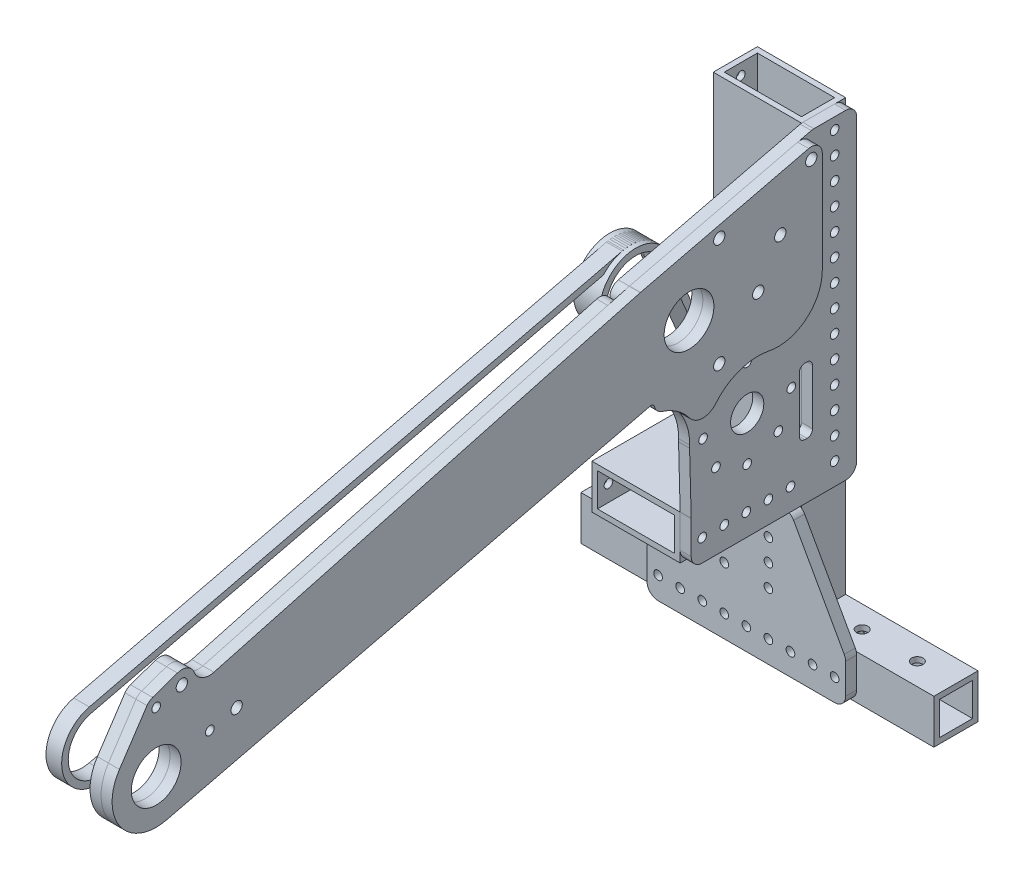
SolidWorks part; units mm, degrees
ref_plane "Alzado" through (0, 0, 0) normal (0, 0, 1) x (1, 0, 0)
ref_plane "Planta" through (0, 0, 0) normal (0, 1, 0) x (1, 0, 0)
ref_plane "Vista lateral" through (0, 0, 0) normal (1, 0, 0) x (0, 0, -1)
sketch "Croquis1" plane through (0, 0, 0) normal (0, 1, 0) x (1, 0, 0)
  line L1 (-101.6, -12.7) -> (101.6, -12.7)
  line L2 (-101.6, -12.7) -> (-101.6, 12.7)
  line L3 (-101.6, 12.7) -> (101.6, 12.7)
  line L4 (101.6, -12.7) -> (101.6, 12.7)
  line L5 (-101.6, -12.7) -> (101.6, 12.7) construction
  line L6 (-101.6, 12.7) -> (101.6, -12.7) construction
  point P0 (0, 0)
  dimension "D1" = 25.4
  dimension "D2" = 203.2
extrude "Saliente-Extruir1" add sketch "Croquis1" along normal blind 25.4
shell "Vaciado1" thickness 3.175 removed face at (-101.6, 12.7, 0) removed face at (101.6, 12.7, 0)
sketch "Croquis2" plane through (0, 25.4, 0) normal (0, 1, 0) x (1, 0, 0)
  line L0 (101.6, 12.7) -> (-101.6, 12.7) construction
  line L1 (-25.4, -12.7) -> (25.4, -12.7)
  line L2 (-25.4, -12.7) -> (-25.4, 12.7)
  line L3 (-25.4, 12.7) -> (25.4, 12.7)
  line L4 (25.4, -12.7) -> (25.4, 12.7)
  line L5 (-25.4, -12.7) -> (25.4, 12.7) construction
  line L6 (-25.4, 12.7) -> (25.4, -12.7) construction
  line L8 (-22.225, -9.525) -> (22.225, -9.525)
  line L9 (-22.225, -9.525) -> (-22.225, 9.525)
  line L10 (-22.225, 9.525) -> (22.225, 9.525)
  line L11 (22.225, -9.525) -> (22.225, 9.525)
  line L12 (-22.225, -9.525) -> (22.225, 9.525) construction
  line L13 (-22.225, 9.525) -> (22.225, -9.525) construction
  point P0 (0, 0)
  point P8 (0, 0)
  dimension "D1" = 50.8
  dimension "D2" = 3.175
  dimension "D3" = 3.175
extrude "Saliente-Extruir2" add sketch "Croquis2" along normal blind 247.65 separate body
sketch "Croquis3" plane through (0, 25.4, 0) normal (0, 1, 0) x (1, 0, 0)
  line L0 (0, 0) -> (0, 12.7) construction
  line L1 (25.4, 12.7) -> (-25.4, 12.7) construction
  circle A0 centre (-47.625, 0) radius 3.2639
  circle A1 centre (-79.375, 0) radius 3.2639
  circle A2 centre (79.375, 0) radius 3.2639
  circle A3 centre (47.625, 0) radius 3.2639
  dimension "D1" = 47.625
  dimension "D2" = 6.5278
  dimension "D3" = 31.75
extrude "Cortar-Extruir1" cut sketch "Croquis3" against normal through all
sketch "Croquis4" plane through (0, 0, 12.7) normal (0, 0, 1) x (1, 0, 0)
  line L0 (0, 25.4) -> (0, 139.6619) construction
  line L1 (-101.6, 25.4) -> (101.6, 25.4) construction
  line L2 (0, 139.6619) -> (-23.8125, 139.6619) construction
  circle A0 centre (0, 139.6619) radius 14.3129
  circle A1 centre (0, 139.6619) radius 23.8125 construction
  circle A2 centre (-23.8125, 139.6619) radius 2.4892 construction
  circle A3 centre (-11.9062, 160.2841) radius 2.4892
  circle A4 centre (11.9063, 160.2841) radius 2.4892
  circle A5 centre (23.8125, 139.6619) radius 2.4892 construction
  circle A6 centre (11.9062, 119.0397) radius 2.4892
  circle A7 centre (-11.9063, 119.0397) radius 2.4892
  dimension "D1" = 28.6258
  dimension "D3" = 47.625
  dimension "D4" = 4.9784
  dimension "D2" = 114.2619
  dimension "D6" = 23.8125
  dimension "D5" = 6
extrude "Cortar-Extruir2" cut sketch "Croquis4" against normal through all
sketch "Croquis8" plane through (0, 0, 12.7) normal (0, 0, 1) x (1, 0, 0)
  line L0 (0, 0) -> (0, 273.05) construction
  line L1 (-101.6, 12.7) -> (0, 12.7) construction
  line L2 (-101.6, 25.4) -> (-101.6, 0) construction
  line L3 (0, 12.7) -> (-12.7, 12.7) construction
  line L4 (0, 12.7) -> (12.7, 12.7) construction
  line L5 (-25.4, 273.05) -> (25.4, 273.05) construction
  line L6 (-12.7, 12.7) -> (-12.7, 25.4) construction
  circle A0 centre (0, 12.7) radius 2.4892
  circle A1 centre (-12.7, 12.7) radius 2.4892
  circle A2 centre (-25.4, 12.7) radius 2.4892
  circle A3 centre (-38.1, 12.7) radius 2.4892
  circle A4 centre (-50.8, 12.7) radius 2.4892
  circle A5 centre (0, 12.7) radius 2.4892
  circle A6 centre (-12.7, 12.7) radius 2.4892
  circle A7 centre (-25.4, 12.7) radius 2.4892
  circle A8 centre (-38.1, 12.7) radius 2.4892
  circle A9 centre (12.7, 12.7) radius 2.4892
  circle A10 centre (0, 12.7) radius 2.4892
  circle A11 centre (-12.7, 12.7) radius 2.4892
  circle A12 centre (-25.4, 12.7) radius 2.4892
  circle A13 centre (25.4, 12.7) radius 2.4892
  circle A14 centre (12.7, 12.7) radius 2.4892
  circle A15 centre (0, 12.7) radius 2.4892
  circle A16 centre (-12.7, 12.7) radius 2.4892
  circle A17 centre (38.1, 12.7) radius 2.4892
  circle A18 centre (25.4, 12.7) radius 2.4892
  circle A19 centre (12.7, 12.7) radius 2.4892
  circle A20 centre (0, 12.7) radius 2.4892
  circle A21 centre (12.7, 12.7) radius 2.4892
  circle A22 centre (25.4, 12.7) radius 2.4892
  circle A23 centre (38.1, 12.7) radius 2.4892
  circle A24 centre (50.8, 12.7) radius 2.4892
  circle A25 centre (-12.7, 25.4) radius 2.4892 [skipped]
  circle A26 centre (12.7, 25.4) radius 2.4892 [skipped]
  circle A27 centre (-12.7, 38.1) radius 2.4892
  circle A28 centre (12.7, 38.1) radius 2.4892
  circle A29 centre (-12.7, 50.8) radius 2.4892
  circle A30 centre (12.7, 50.8) radius 2.4892
  circle A31 centre (-12.7, 63.5) radius 2.4892
  circle A32 centre (12.7, 63.5) radius 2.4892
  circle A33 centre (-12.7, 76.2) radius 2.4892
  circle A34 centre (12.7, 76.2) radius 2.4892
  dimension "D1" = 4.9784
  dimension "D4" = 12.7
  dimension "D5" = 12.7
  dimension "D7" = 12.7
  dimension "D2" = 5
  dimension "D3" = 5
  dimension "D6" = 6
extrude "Cortar-Extruir4" cut sketch "Croquis8" against normal through all contours A4 | A3 | A2 | A1 | A0 | A9 | A13 | A17 | A24 | A28 | A29 | A30 | A31 | A32 | A34 | A33 | A27 region at (0, 12.7, 12.7) region at (-12.7, 12.7, 12.7) region at (-25.4, 12.7, 12.7) region at (-38.1, 12.7, 12.7) region at (-50.8, 12.7, 12.7) region at (12.7, 12.7, 12.7) region at (25.4, 12.7, 12.7) region at (38.1, 12.7, 12.7) region at (50.8, 12.7, 12.7) region at (12.7, 38.1, 12.7) region at (-12.7, 50.8, 12.7) region at (12.7, 50.8, 12.7) region at (-12.7, 63.5, 12.7) region at (12.7, 63.5, 12.7) region at (-12.7, 76.2, 12.7) region at (12.7, 76.2, 12.7)
sketch "Croquis6" plane through (0, 0, 12.7) normal (0, 0, 1) x (1, 0, 0)
  line L0 (25.4, 273.05) -> (25.4, 25.4) construction
  line L1 (-25.4, 88.646) -> (25.4, 88.646)
  line L2 (-25.4, 88.646) -> (-25.4, 114.046)
  line L3 (-25.4, 114.046) -> (25.4, 114.046)
  line L4 (25.4, 88.646) -> (25.4, 114.046)
  line L5 (-25.4, 88.646) -> (25.4, 114.046) construction
  line L6 (-25.4, 114.046) -> (25.4, 88.646) construction
  line L7 (-101.6, 25.4) -> (101.6, 25.4) construction
  line L9 (-22.225, 91.821) -> (22.225, 91.821)
  line L10 (-22.225, 91.821) -> (-22.225, 110.871)
  line L11 (-22.225, 110.871) -> (22.225, 110.871)
  line L12 (22.225, 91.821) -> (22.225, 110.871)
  line L13 (-22.225, 91.821) -> (22.225, 110.871) construction
  line L14 (-22.225, 110.871) -> (22.225, 91.821) construction
  point P0 (0, 101.346)
  point P11 (0, 101.346)
  dimension "D1" = 25.4
  dimension "D2" = 63.246
  dimension "D3" = 3.175
  dimension "D4" = 3.175
extrude "Saliente-Extruir3" add sketch "Croquis6" along normal blind 69.85 separate body
sketch "Croquis7" plane through (0, 114.046, 0) normal (0, 1, 0) x (1, 0, 0)
  line L0 (0, -12.7) -> (0, -82.55) construction
  line L1 (-25.4, -12.7) -> (25.4, -12.7) construction
  line L2 (25.4, -82.55) -> (-25.4, -82.55) construction
  line L3 (16.51, -12.7) -> (-16.51, -12.7)
  line L4 (25.4, -12.7) -> (-25.4, -12.7) construction
  line L5 (-16.51, -12.7) -> (-16.51, -34.798)
  line L6 (-13.208, -38.1) -> (13.208, -38.1)
  line L7 (16.51, -12.7) -> (16.51, -34.798)
  arc A0 (16.51, -34.798) -> (13.208, -38.1) centre (13.208, -34.798) cw
  arc A1 (-16.51, -34.798) -> (-13.208, -38.1) centre (-13.208, -34.798) ccw
  point P12 (0, -38.1)
  point P16 (16.51, -38.1)
  point P19 (-16.51, -38.1)
  dimension "D3" = 3.302
  dimension "D1" = 25.4
  dimension "D2" = 33.02
extrude "Cortar-Extruir3" cut sketch "Croquis7" against normal up to next (3.175 mm away)
sketch "Croquis11" plane through (25.4, 0, 0) normal (1, 0, 0) x (0, 0, -1)
  line L0 (0, -101.854) -> (-381, -101.854) construction
  line L1 (-82.55, 88.646) -> (-82.55, 114.046) construction
  line L2 (-82.55, 88.646) -> (-12.7, 88.646) construction
  line L6 (-517.96, -101.854) -> (-276.66, -101.854) construction
  line L7 (-517.96, -101.854) -> (-517.96, 139.446) construction
  line L8 (-517.96, 139.446) -> (-276.66, 139.446) construction
  line L9 (-276.66, -101.854) -> (-276.66, 139.446) construction
  circle A0 centre (-396.875, 145.796) radius 38.1
  dimension "D3" = 76.2
  dimension "D4" = 209.55
  dimension "D5" = 276.225
  dimension "D1" = 190.5
  dimension "D2" = 381
  dimension "D6" = 241.3
sketch "Croquis9" plane through (0, 0, 12.7) normal (0, 0, 1) x (1, 0, 0)
  line L0 (0, 0) -> (0, 273.05) construction
  line L1 (-25.4, 273.05) -> (25.4, 273.05) construction
  line L2 (50.8, 0) -> (-50.8, 0)
  line L3 (-101.6, 0) -> (101.6, 0) construction
  line L4 (-57.15, 6.35) -> (-57.15, 23.7481)
  line L5 (-101.6, 25.4) -> (101.6, 25.4) construction
  line L6 (-56.3451, 26.8425) -> (-27.2168, 79.0403)
  line L7 (-25.4, 273.05) -> (-25.4, 25.4) construction
  line L8 (-21.6717, 82.296) -> (21.6717, 82.296)
  line L9 (56.3451, 26.8425) -> (27.2168, 79.0403)
  line L10 (57.15, 6.35) -> (57.15, 23.7481)
  line L11 (-25.4, 88.646) -> (25.4, 88.646) construction
  circle A0 centre (-50.8, 12.7) radius 2.4892 construction
  arc A2 (-50.8, 0) -> (-57.15, 6.35) centre (-50.8, 6.35) cw
  arc A3 (-57.15, 23.7481) -> (-56.3451, 26.8425) centre (-50.8, 23.7481) cw
  arc A4 (-27.2168, 79.0403) -> (-21.6717, 82.296) centre (-21.6717, 75.946) cw
  arc A5 (27.2168, 79.0403) -> (21.6717, 82.296) centre (21.6717, 75.946) ccw
  arc A6 (57.15, 23.7481) -> (56.3451, 26.8425) centre (50.8, 23.7481) ccw
  arc A7 (50.8, 0) -> (57.15, 6.35) centre (50.8, 6.35) ccw
  circle A9 centre (-25.4, 12.7) radius 2.4892
  circle A10 centre (-25.4, 12.7) radius 2.4892
  circle A11 centre (-12.7, 12.7) radius 2.4892
  circle A12 centre (-12.7, 12.7) radius 2.4892
  circle A13 centre (0, 12.7) radius 2.4892
  circle A14 centre (0, 12.7) radius 2.4892
  circle A15 centre (0, 12.7) radius 2.4892
  circle A16 centre (0, 12.7) radius 2.4892
  circle A17 centre (12.7, 12.7) radius 2.4892
  circle A18 centre (12.7, 12.7) radius 2.4892
  circle A19 centre (-38.1, 12.7) radius 2.4892
  circle A20 centre (-38.1, 12.7) radius 2.4892
  circle A21 centre (-25.4, 12.7) radius 2.4892
  circle A22 centre (-25.4, 12.7) radius 2.4892
  circle A23 centre (-12.7, 12.7) radius 2.4892
  circle A24 centre (-12.7, 12.7) radius 2.4892
  circle A25 centre (0, 12.7) radius 2.4892
  circle A26 centre (0, 12.7) radius 2.4892
  circle A27 centre (-50.8, 12.7) radius 2.4892
  circle A28 centre (-50.8, 12.7) radius 2.4892
  circle A29 centre (-38.1, 12.7) radius 2.4892
  circle A30 centre (-38.1, 12.7) radius 2.4892
  circle A31 centre (25.4, 12.7) radius 2.4892
  circle A32 centre (25.4, 12.7) radius 2.4892
  circle A33 centre (38.1, 12.7) radius 2.4892
  circle A34 centre (38.1, 12.7) radius 2.4892
  circle A35 centre (-12.7, 12.7) radius 2.4892
  circle A36 centre (-12.7, 12.7) radius 2.4892
  circle A37 centre (0, 12.7) radius 2.4892
  circle A38 centre (0, 12.7) radius 2.4892
  circle A39 centre (12.7, 12.7) radius 2.4892
  circle A40 centre (12.7, 12.7) radius 2.4892
  circle A41 centre (25.4, 12.7) radius 2.4892
  circle A42 centre (25.4, 12.7) radius 2.4892
  circle A43 centre (-25.4, 12.7) radius 2.4892
  circle A44 centre (-25.4, 12.7) radius 2.4892
  circle A45 centre (-12.7, 12.7) radius 2.4892
  circle A46 centre (-12.7, 12.7) radius 2.4892
  circle A47 centre (50.8, 12.7) radius 2.4892
  circle A48 centre (50.8, 12.7) radius 2.4892
  circle A49 centre (38.1, 12.7) radius 2.4892
  circle A50 centre (38.1, 12.7) radius 2.4892
  circle A51 centre (25.4, 12.7) radius 2.4892
  circle A52 centre (25.4, 12.7) radius 2.4892
  circle A53 centre (12.7, 12.7) radius 2.4892
  circle A54 centre (12.7, 12.7) radius 2.4892
  circle A55 centre (0, 12.7) radius 2.4892
  circle A56 centre (0, 12.7) radius 2.4892
  circle A57 centre (12.7, 12.7) radius 2.4892
  circle A58 centre (12.7, 12.7) radius 2.4892
  circle A59 centre (-12.7, 76.2) radius 2.4892
  circle A60 centre (-12.7, 76.2) radius 2.4892
  circle A61 centre (12.7, 63.5) radius 2.4892
  circle A62 centre (12.7, 63.5) radius 2.4892
  circle A63 centre (-12.7, 63.5) radius 2.4892
  circle A64 centre (-12.7, 63.5) radius 2.4892
  circle A65 centre (12.7, 50.8) radius 2.4892
  circle A66 centre (12.7, 50.8) radius 2.4892
  circle A67 centre (-12.7, 50.8) radius 2.4892
  circle A68 centre (-12.7, 50.8) radius 2.4892
  circle A69 centre (12.7, 38.1) radius 2.4892
  circle A70 centre (12.7, 38.1) radius 2.4892
  circle A71 centre (-12.7, 38.1) radius 2.4892
  circle A72 centre (-12.7, 38.1) radius 2.4892
  circle A73 centre (12.7, 76.2) radius 2.4892
  circle A74 centre (12.7, 76.2) radius 2.4892
  point P22 (-57.15, 0)
  point P25 (-57.15, 25.4)
  point P28 (-25.4, 82.296)
  point P38 (0, 82.296)
  dimension "D1" = 6.35
  dimension "D3" = 6.35
  dimension "D37" = 6.35
  dimension "D4" = 0
  dimension "D5" = 0
  dimension "D6" = 0
  dimension "D7" = 0
  dimension "D8" = 0
  dimension "D9" = 0
  dimension "D10" = 0
  dimension "D11" = 0
  dimension "D12" = 0
  dimension "D13" = 0
  dimension "D14" = 0
  dimension "D15" = 0
  dimension "D16" = 0
  dimension "D17" = 0
  dimension "D18" = 0
  dimension "D19" = 0
  dimension "D20" = 0
  dimension "D21" = 0
  dimension "D22" = 0
  dimension "D23" = 0
  dimension "D24" = 0
  dimension "D25" = 0
  dimension "D26" = 0
  dimension "D27" = 0
  dimension "D28" = 0
  dimension "D29" = 0
  dimension "D30" = 0
  dimension "D31" = 0
  dimension "D32" = 0
  dimension "D33" = 0
  dimension "D34" = 0
  dimension "D35" = 0
  dimension "D36" = 0
extrude "Saliente-Extruir4" add sketch "Croquis9" along normal blind 6.35 separate body contours L0 L8 A4 L6 A3 A60 A64 A68 A72 | L0 A6 L9 A5 L8 A74 A70 A66 A62 | L0 A3 L4 A2 | L0 L2 A7 L10 A6 A56 region at (-24.3725, 36.0328, 12.7) region at (24.3725, 36.0328, 12.7)
sketch "Croquis15" plane through (25.4, 0, 0) normal (1, 0, 0) x (0, 0, -1)
  line L0 (-12.7, 0) -> (-12.7, 171.1325) construction
  line L1 (-12.7, 273.05) -> (-12.7, 25.4) construction
  line L2 (-72.5746, 227.1642) -> (-41.5317, 154.1315) construction
  line L3 (-105.4538, 208.2656) -> (-57.9713, 144.6822) construction
  line L4 (-94.6246, 238.2605) -> (-401.3483, 164.3633) construction
  line L5 (-392.4017, 127.2287) -> (-85.6779, 201.1258) construction
  line L8 (-82.55, 114.046) -> (-12.7, 114.046) construction
  circle A0 centre (-50.32, 150.396) radius 30
  arc A1 (-57.9713, 144.6822) -> (-41.5317, 154.1315) centre (-50.32, 150.396) ccw construction
  arc A2 (-401.3483, 164.3633) -> (-392.4017, 127.2287) centre (-396.875, 145.796) ccw construction
  arc A3 (-72.5746, 227.1642) -> (-105.4538, 208.2656) centre (-90.1513, 219.6932) ccw construction
  arc A4 (-85.6779, 201.1258) -> (-94.6246, 238.2605) centre (-90.1513, 219.6932) ccw construction
  dimension "D2" = 60
  dimension "D3" = 19.0986
  dimension "D4" = 38.1972
  dimension "D1" = 171.1325
  dimension "D7" = 6.35
  dimension "D8" = 7.62
sketch "Croquis16" plane through (25.4, 0, 0) normal (1, 0, 0) x (0, 0, -1)
  line L0 (-50.32, 150.396) -> (-50.32, 175.796) construction
  line L1 (-13.4332, 272.8734) -> (-118.1525, 247.644)
  line L2 (-82.55, 94.996) -> (-82.55, 113.9625)
  line L3 (-82.5522, 114.1295) -> (-83.4835, 149.5234)
  line L4 (-76.2, 88.646) -> (6.35, 88.646)
  line L5 (12.7, 273.05) -> (12.7, 25.4) construction
  line L6 (12.7, 94.996) -> (12.7, 266.7)
  line L7 (6.35, 273.05) -> (-11.9459, 273.05)
  line L8 (-94.6246, 238.2605) -> (-401.3483, 164.3633) construction
  line L9 (-122.8385, 239.9833) -> (-110.0117, 186.743)
  line L10 (-90.1513, 219.6932) -> (-116.4251, 213.3632) construction
  circle A0 centre (-90.1513, 219.6932) radius 14.3256
  circle A1 centre (-50.32, 150.396) radius 33.175
  circle A4 centre (-50.32, 150.396) radius 9.5631
  circle A5 centre (-50.32, 150.396) radius 25.4 construction
  circle A6 centre (-50.32, 175.796) radius 2.4892
  circle A7 centre (-32.3595, 168.3565) radius 2.4892 construction
  circle A8 centre (-24.92, 150.396) radius 2.4892
  circle A9 centre (-32.3595, 132.4355) radius 2.4892
  circle A10 centre (-50.32, 124.996) radius 2.4892
  circle A11 centre (-68.2805, 132.4355) radius 2.4892
  circle A12 centre (-75.72, 150.396) radius 2.4892
  circle A13 centre (-68.2805, 168.3565) radius 2.4892
  arc A18 (-105.7366, 182.1707) -> (-83.4864, 151.1506) centre (-115.2282, 151.8727) cw
  arc A19 (-110.0117, 186.743) -> (-105.7366, 182.1707) centre (-103.8383, 188.2304) ccw
  arc A21 (-118.1525, 247.644) -> (-122.8385, 239.9833) centre (-116.6652, 241.4706) ccw
  arc A23 (-11.9459, 273.05) -> (-13.4332, 272.8734) centre (-11.9459, 266.7) ccw
  circle A26 centre (-50.32, 150.396) radius 30 construction
  arc A29 (-82.55, 113.9625) -> (-82.5522, 114.1295) centre (-88.9, 113.9625) ccw
  arc A31 (12.7, 266.7) -> (6.35, 273.05) centre (6.35, 266.7) ccw
  arc A32 (6.35, 88.646) -> (12.7, 94.996) centre (6.35, 94.996) ccw
  arc A33 (-82.55, 94.996) -> (-76.2, 88.646) centre (-76.2, 94.996) ccw
  point P45 (-12.7, 273.05)
  point P72 (-82.55, 114.046)
  point P74 (12.7, 273.05)
  point P77 (12.7, 88.646)
  point P80 (-82.55, 88.646)
  dimension "D1" = 28.6512
  dimension "D2" = 3.175
  dimension "D3" = 31.75
  dimension "D4" = 19.1262
  dimension "D5" = 50.8
  dimension "D6" = 4.9784
  dimension "D9" = 6.35
  dimension "D10" = 6.35
  dimension "D14" = 6.35
  dimension "D15" = 6.35
  dimension "D12" = 6.35
  dimension "D8" = 25.4
  dimension "D11" = 12.7
  dimension "D7" = 8
extrude "Saliente-Extruir5" add sketch "Croquis16" along normal blind 6.35 separate body contours L4 A32 A31 A23 | L2 A33 L4 A23 L1 A21 L9 A19 A18 A1 L3 A29 A0 | A1 A13 A12 A11 A10 A9 A8 A6 A4 region at (25.4, 188.5949, 38.9873) region at (25.4, 182.6306, 49.9534)
sketch "Croquis12" plane through (25.4, 0, 0) normal (1, 0, 0) x (0, 0, -1)
  line L0 (-82.55, 101.346) -> (-12.7, 101.346) construction
  line L1 (-82.55, 88.646) -> (-82.55, 114.046) construction
  line L2 (-12.7, 88.646) -> (-12.7, 114.046) construction
  line L3 (0, 273.05) -> (0, 0) construction
  line L4 (-12.7, 273.05) -> (12.7, 273.05) construction
  line L5 (0, 101.346) -> (-12.7, 101.346) construction
  line L6 (0, 101.346) -> (0, 114.046) construction
  circle A1 centre (0, 101.346) radius 2.4892
  circle A2 centre (-12.7, 101.346) radius 2.4892 [skipped]
  circle A3 centre (-25.4, 101.346) radius 2.4892
  circle A4 centre (-38.1, 101.346) radius 2.4892
  circle A5 centre (-50.8, 101.346) radius 2.4892
  circle A6 centre (0, 114.046) radius 2.4892
  circle A7 centre (0, 126.746) radius 2.4892
  circle A8 centre (0, 139.446) radius 2.4892
  circle A9 centre (0, 152.146) radius 2.4892
  circle A10 centre (0, 164.846) radius 2.4892
  circle A11 centre (0, 177.546) radius 2.4892
  circle A12 centre (0, 190.246) radius 2.4892
  circle A13 centre (0, 202.946) radius 2.4892
  circle A14 centre (0, 215.646) radius 2.4892
  circle A15 centre (0, 228.346) radius 2.4892
  circle A16 centre (0, 241.046) radius 2.4892
  circle A17 centre (0, 253.746) radius 2.4892
  circle A18 centre (0, 266.446) radius 2.4892
  circle A19 centre (-63.5, 101.346) radius 2.4892
  circle A20 centre (-76.2, 101.346) radius 2.4892
  dimension "D1" = 4.9784
  dimension "D3" = 12.7
  dimension "D5" = 12.7
  dimension "D2" = 7
  dimension "D4" = 14
extrude "Cortar-Extruir5" cut sketch "Croquis12" against normal through all and the other way through all
sketch "Croquis17" plane through (31.75, 0, 0) normal (1, 0, 0) x (0, 0, -1)
  line L0 (-403.5186, 170.3118) -> (-118.2389, 247.6205)
  line L1 (-118.0654, 247.6649) -> (-21.2705, 270.9852)
  line L2 (-390.9258, 121.1026) -> (-118.1525, 186.8202)
  line L3 (-392.4017, 127.2287) -> (-85.6779, 201.1258) construction
  line L4 (-118.1525, 186.8202) -> (-112.4025, 188.2055)
  line L5 (-13.4332, 206.3797) -> (-13.4332, 264.8118)
  line L6 (-398.9636, 186.2074) -> (-384.6217, 191.2027)
  line L7 (-402.1634, 183.7258) -> (-418.0287, 159.8559)
  circle A0 centre (-396.875, 145.796) radius 14.3256
  circle A1 centre (-90.1513, 219.6932) radius 14.3256
  circle A2 centre (-396.875, 145.796) radius 25.4
  arc A3 (-118.2389, 247.6205) -> (-118.0654, 247.6649) centre (-116.578, 241.4916) cw
  arc A4 (-21.2705, 270.9852) -> (-13.4332, 264.8118) centre (-19.7832, 264.8118) cw
  arc A5 (-13.4332, 206.3797) -> (-43.9384, 181.4981) centre (-38.8332, 206.3797) cw
  circle A6 centre (-50.32, 150.396) radius 31.75
  arc A8 (-110.0117, 186.743) -> (-105.7366, 182.1707) centre (-103.8383, 188.2304) ccw construction
  arc A9 (-110.0117, 186.743) -> (-105.7366, 182.1707) centre (-103.8383, 188.2304) ccw
  arc A10 (-110.0117, 186.743) -> (-112.4025, 188.2055) centre (-111.9383, 186.2789) ccw
  arc A11 (-83.4864, 151.1506) -> (-105.7366, 182.1707) centre (-115.2282, 151.8727) ccw construction
  arc A12 (-89.8175, 170.9084) -> (-105.7366, 182.1707) centre (-115.2282, 151.8727) ccw
  arc A13 (-89.8175, 170.9084) -> (-74.8387, 170.5677) centre (-82.1943, 176.6192) ccw
  circle A14 centre (-396.875, 180.2108) radius 6.35
  circle A15 centre (-382.1153, 184.0067) radius 7.62
  arc A17 (-375.0276, 186.8047) -> (-363.6766, 181.1087) centre (-366.1679, 190.3021) ccw
  point P19 (-118.1525, 247.644)
  point P23 (-13.4332, 272.8734)
  line M28 (-13.4332, 272.8734) -> (-118.1525, 247.644)
  arc M29 (-118.1525, 247.644) -> (-122.8385, 239.9833) centre (-116.6652, 241.4706) ccw
  line M30 (-122.8385, 239.9833) -> (-110.0117, 186.743)
  circle M38 centre (-90.1513, 219.6932) radius 14.3256
  dimension "D1" = 28.6512
  dimension "D2" = 50.8
  dimension "D3" = 6.35
  dimension "D4" = 63.5
  dimension "D5" = 9.525
  dimension "D6" = 25.4
  dimension "D7" = 12.7
  dimension "D8" = 34.4148
  dimension "D9" = 15.24
  dimension "D10" = 15.24
  dimension "D11" = 9.525
extrude "Saliente-Extruir6" add sketch "Croquis17" along normal blind 6.35 separate body contours A2 L2 L0 M30 M29 | L5 A4 A3 L0 M28 M29 M30 M38 | A2 A0 | A14 L7 A2 L0 | A14 | A15 | A17 A15 L0 region at (31.75, 166.8023, 412.0119) region at (31.75, 184.8147, 244.5216) region at (31.75, 165.3985, 381.8776) region at (31.75, 180.6264, 372.6967) region at (31.75, 184.0067, 382.1153) region at (31.75, 180.2108, 396.875) region at (31.75, 220.7032, 61.6214)
sketch "Croquis18" plane through (38.1, 0, 0) normal (1, 0, 0) x (0, 0, -1)
  line L0 (-122.8385, 239.9833) -> (-110.0117, 186.743) construction
  line L1 (-122.754, 239.6323) -> (-111.9631, 194.8431)
  line L2 (-403.5186, 170.3118) -> (-118.2389, 247.6205) construction
  line L3 (-402.1634, 183.7258) -> (-418.0287, 159.8559) construction
  line L4 (-398.9636, 186.2074) -> (-384.6217, 191.2027) construction
  line L5 (-402.1634, 183.7258) -> (-418.0287, 159.8559)
  line L6 (-390.9258, 121.1026) -> (-118.1525, 186.8202) construction
  line L7 (-403.5186, 170.3118) -> (-130.5882, 244.274)
  line L8 (-398.9636, 186.2074) -> (-384.6217, 191.2027)
  line L10 (-122.8385, 239.9833) -> (-110.0117, 186.743) construction
  line L11 (-390.9258, 121.1026) -> (-116.6492, 187.1824)
  circle A1 centre (-396.875, 145.796) radius 25.4
  circle A2 centre (-396.875, 145.796) radius 25.4
  arc A3 (-116.6492, 187.1824) -> (-111.9631, 194.8431) centre (-118.1365, 193.3558) ccw
  circle A5 centre (-396.875, 145.796) radius 14.3256
  circle A6 centre (-396.875, 145.796) radius 14.3256
  arc A12 (-122.754, 239.6323) -> (-130.5882, 244.274) centre (-128.9273, 238.145) ccw
  circle A14 centre (-396.875, 180.2108) radius 6.35 construction
  arc A15 (-375.0276, 186.8047) -> (-363.6766, 181.1087) centre (-366.1679, 190.3021) ccw construction
  circle A16 centre (-396.875, 180.2108) radius 6.35
  arc A17 (-375.0276, 186.8047) -> (-384.6217, 191.2027) centre (-382.1153, 184.0067) ccw construction
  arc A18 (-375.0276, 186.8047) -> (-363.6766, 181.1087) centre (-366.1679, 190.3021) ccw
  arc A19 (-375.0276, 186.8047) -> (-384.6217, 191.2027) centre (-382.1153, 184.0067) ccw
  point P18 (-110.4758, 188.6697)
  line M10 (-118.2389, 247.6205) -> (-363.6766, 181.1087)
  arc M11 (-418.0287, 159.8559) -> (-390.9258, 121.1026) centre (-396.875, 145.796) ccw
  circle M13 centre (-396.875, 145.796) radius 14.3256
  line M33 (-402.1634, 183.7258) -> (-418.0287, 159.8559)
  arc M35 (-398.9636, 186.2074) -> (-402.1634, 183.7258) centre (-396.875, 180.2108) ccw
  dimension "D2" = 6.35
  dimension "D1" = 0
  dimension "D3" = 0
extrude "Saliente-Extruir7" add sketch "Croquis18" along normal blind 6.35 from surface separate body contours L1 A12 A2 A3 M10 | A2 M11 M13 | A16 A2 L7 M33 | A16 M35 region at (38.1, 184.7417, 244.7476) region at (38.1, 180.3032, 388.6206) region at (38.1, 131.6506, 417.1009) region at (38.1, 180.2108, 396.875) starting at face at (25.4, 101.346, -2.4892)
sketch "Croquis22" plane through (38.1, 0, 0) normal (1, 0, 0) x (0, 0, -1)
  line L0 (-396.875, 145.796) -> (-90.1513, 219.6932) construction
  line L1 (-90.1513, 219.6932) -> (-50.32, 150.396) construction
  line L4 (-50.32, 236.121) -> (-37.62, 236.121) construction
  line L5 (-21.2705, 270.9852) -> (-118.0654, 247.6649) construction
  circle A0 centre (-396.875, 180.2108) radius 2.4892
  circle A1 centre (-350.5748, 156.9508) radius 3.2639
  circle A2 centre (-396.875, 145.796) radius 19.0986 construction
  arc A3 (-401.3483, 164.3633) -> (-392.4017, 127.2287) centre (-396.875, 145.796) ccw construction
  circle A4 centre (-350.5748, 156.9508) radius 6.35 construction
  circle A7 centre (-72.747, 189.4137) radius 3.2639
  circle A8 centre (-72.747, 189.4137) radius 6.35 construction
  circle A9 centre (-50.32, 213.896) radius 6.35 construction
  circle A10 centre (-50.32, 213.896) radius 3.2639
  circle A13 centre (-37.62, 236.121) radius 3.2639
  circle A14 centre (-37.62, 236.121) radius 6.35 construction
  circle A15 centre (-72.747, 252.0515) radius 3.2639
  circle A16 centre (-72.747, 252.0515) radius 6.35 construction
  circle A17 centre (-19.7832, 264.8118) radius 6.35 construction
  circle A18 centre (-19.7832, 264.8118) radius 3.2639
  circle A19 centre (-382.1153, 184.0067) radius 3.2639
  circle A20 centre (-366.0082, 153.2326) radius 2.4892
  circle A21 centre (-366.0082, 153.2326) radius 4.7625 construction
  dimension "D1" = 6.5278
  dimension "D2" = 47.625
  dimension "D3" = 12.7
  dimension "D4" = 34.925
  dimension "D5" = 63.5
  dimension "D6" = 22.225
  dimension "D7" = 12.7
  dimension "D8" = 4.9784
  dimension "D9" = 6.5278
  dimension "D10" = 9.525
  dimension "D11" = 31.75
extrude "Cortar-Extruir6" cut sketch "Croquis22" against normal through all
sketch "Croquis24" plane through (38.1, 0, 0) normal (1, 0, 0) x (0, 0, -1)
  line L0 (-396.875, 145.796) -> (-90.1513, 219.6932) construction
  line L1 (-243.5131, 182.7446) -> (-247.9864, 201.3119) construction
  line L2 (-94.6246, 238.2605) -> (-401.3483, 164.3633) construction
  circle A0 centre (-295.9867, 170.1024) radius 2.4892
  circle A1 centre (-191.0395, 195.3867) radius 2.4892
  circle A2 centre (-243.5131, 182.7446) radius 2.4892
  circle A3 centre (-147.826, 205.7979) radius 2.4892
  dimension "D1" = 4.9784
  dimension "D2" = 53.975
  dimension "D3" = 44.45
sketch "Croquis25" plane through (31.75, 0, 0) normal (1, 0, 0) x (0, 0, -1)
  line L0 (-12.7, 0) -> (-12.7, 139.7) construction
  line L1 (-12.7, 123.825) -> (-12.7, 155.575)
  line L2 (-12.7, 0) -> (-12.7, 171.1325) construction
  line L3 (-15.875, 158.75) -> (-17.145, 158.75)
  line L4 (-20.32, 155.575) -> (-20.32, 123.825)
  line L5 (-12.7, 139.7) -> (-20.32, 139.7) construction
  line L6 (-15.875, 120.65) -> (-17.145, 120.65)
  arc A0 (-12.7, 155.575) -> (-15.875, 158.75) centre (-15.875, 155.575) ccw
  arc A1 (-15.875, 120.65) -> (-12.7, 123.825) centre (-15.875, 123.825) ccw
  arc A2 (-17.145, 120.65) -> (-20.32, 123.825) centre (-17.145, 123.825) cw
  arc A3 (-17.145, 158.75) -> (-20.32, 155.575) centre (-17.145, 155.575) ccw
  point P13 (-12.7, 158.75)
  point P16 (-12.7, 120.65)
  point P19 (-20.32, 120.65)
  point P22 (-20.32, 158.75)
  dimension "D4" = 3.175
  dimension "D1" = 139.7
  dimension "D2" = 7.62
  dimension "D3" = 38.1
extrude "Cortar-Extruir8" cut sketch "Croquis25" against normal through all
extrude "Cortar-Extruir9" [suppressed] cut sketch "Croquis24" against normal through all
delete or keep bodies "Sólido-Eliminar/Conservar 1" [suppressed] type keep bodies bodies 112
delete or keep bodies "Sólido-Eliminar/Conservar 2" [suppressed] type keep bodies bodies 111
delete or keep bodies "Sólido-Eliminar/Conservar 3" [suppressed] type keep bodies bodies 107
delete or keep bodies "Sólido-Eliminar/Conservar 4" [suppressed] type keep bodies bodies 109
delete or keep bodies "Sólido-Eliminar/Conservar 5" [suppressed] type keep bodies bodies 121
delete or keep bodies "Sólido-Eliminar/Conservar 6" [suppressed] type keep bodies bodies 125
sketch "Croquis29" plane through (0, 0, 0) normal (1, 0, 0) x (0, 0, -1)
  line L0 (-392.4017, 127.2287) -> (-85.6779, 201.1258) construction
  line L1 (-94.6246, 238.2605) -> (-401.3483, 164.3633) construction
  line L2 (-392.4017, 127.2287) -> (-85.6779, 201.1258) construction
  line L3 (-94.6246, 238.2605) -> (-401.3483, 164.3633) construction
  line L4 (-392.8842, 129.2314) -> (-86.1604, 203.1285)
  line L5 (-94.1421, 236.2578) -> (-400.8658, 162.3606)
  line L6 (-391.9941, 125.5371) -> (-85.2704, 199.4342)
  line L7 (-95.0321, 239.9521) -> (-401.7559, 166.0549)
  arc A0 (-85.6779, 201.1258) -> (-94.6246, 238.2605) centre (-90.1513, 219.6932) ccw construction
  arc A1 (-401.3483, 164.3633) -> (-392.4017, 127.2287) centre (-396.875, 145.796) ccw construction
  arc A2 (-85.6779, 201.1258) -> (-94.6246, 238.2605) centre (-90.1513, 219.6932) ccw construction
  arc A3 (-401.3483, 164.3633) -> (-392.4017, 127.2287) centre (-396.875, 145.796) ccw construction
  arc A4 (-86.1604, 203.1285) -> (-94.1421, 236.2578) centre (-90.1513, 219.6932) ccw
  arc A5 (-400.8658, 162.3606) -> (-392.8842, 129.2314) centre (-396.875, 145.796) ccw
  arc A6 (-401.7559, 166.0549) -> (-391.9941, 125.5371) centre (-396.875, 145.796) ccw
  arc A7 (-85.2704, 199.4342) -> (-95.0321, 239.9521) centre (-90.1513, 219.6932) ccw
  dimension "D1" = 2.06
  dimension "D2" = 3.8
extrude "Saliente-Extruir9" add sketch "Croquis29" along normal mid plane 9 separate body
sketch "Croquis30" plane through (0, 0, 0) normal (1, 0, 0) x (0, 0, -1)
  line L0 (-72.5746, 227.1642) -> (-41.5317, 154.1315) construction
  line L1 (-105.4538, 208.2656) -> (-57.9713, 144.6822) construction
  line L2 (-72.5746, 227.1642) -> (-41.5317, 154.1315) construction
  line L3 (-105.4538, 208.2656) -> (-57.9713, 144.6822) construction
  line L4 (-74.4704, 226.3584) -> (-43.4275, 153.3257)
  line L5 (-103.8032, 209.4982) -> (-56.3207, 145.9148)
  line L6 (-106.8479, 207.2245) -> (-59.3654, 143.6411)
  line L7 (-70.9732, 227.8449) -> (-39.9303, 154.8122)
  arc A0 (-57.9713, 144.6822) -> (-41.5317, 154.1315) centre (-50.32, 150.396) ccw construction
  arc A1 (-72.5746, 227.1642) -> (-105.4538, 208.2656) centre (-90.1513, 219.6932) ccw construction
  arc A2 (-57.9713, 144.6822) -> (-41.5317, 154.1315) centre (-50.32, 150.396) ccw construction
  arc A3 (-72.5746, 227.1642) -> (-105.4538, 208.2656) centre (-90.1513, 219.6932) ccw construction
  arc A4 (-56.3207, 145.9148) -> (-43.4275, 153.3257) centre (-50.32, 150.396) ccw
  arc A5 (-74.4704, 226.3584) -> (-103.8032, 209.4982) centre (-90.1513, 219.6932) ccw
  arc A6 (-70.9732, 227.8449) -> (-106.8479, 207.2245) centre (-90.1513, 219.6932) ccw
  arc A7 (-59.3654, 143.6411) -> (-39.9303, 154.8122) centre (-50.32, 150.396) ccw
  dimension "D1" = 2.06
  dimension "D2" = 3.8
extrude "Saliente-Extruir10" add sketch "Croquis30" along normal mid plane 15 separate body
delete or keep bodies "Sólido-Eliminar/Conservar 7" [suppressed] type keep bodies bodies 123
delete or keep bodies "Sólido-Eliminar/Conservar 8" [suppressed] type keep bodies bodies 124
sketch "Croquis31" [suppressed] plane through (31.75, 0, 0) normal (1, 0, 0) x (0, 0, -1)
  line L0 (-402.1634, 183.7258) -> (-418.0287, 159.8559) construction
  line L1 (-402.1634, 183.7258) -> (-418.0287, 159.8559)
  line L2 (-361.1143, 149.1863) -> (-377.2995, 129.6108)
  circle A0 centre (-396.875, 180.2108) radius 6.35
  circle A1 centre (-366.0082, 153.2326) radius 6.35
  circle A2 centre (-350.5748, 156.9508) radius 6.35 construction
  arc A3 (-398.9636, 186.2074) -> (-402.1634, 183.7258) centre (-396.875, 180.2108) ccw construction
  circle A4 centre (-396.875, 145.796) radius 25.4
  arc A5 (-418.0287, 159.8559) -> (-390.9258, 121.1026) centre (-396.875, 145.796) ccw construction
  circle A7 centre (-396.875, 145.796) radius 17.4625
  circle A8 centre (-382.1153, 184.0067) radius 7.62 construction
  arc A9 (-375.0276, 186.8047) -> (-384.6217, 191.2027) centre (-382.1153, 184.0067) ccw construction
  arc A10 (-391.2071, 183.0739) -> (-363.9295, 159.2327) centre (-348.1311, 204.8335) ccw
  dimension "D1" = 12.7
  dimension "D2" = 34.925
  dimension "D3" = 48.26
extrude "Saliente-Extruir11" [suppressed] add sketch "Croquis31" along normal blind 1.5875 separate body
delete or keep bodies "Sólido-Eliminar/Conservar 9" [suppressed] type keep bodies bodies 126
delete or keep bodies "Sólido-Eliminar/Conservar 10" [suppressed] type keep bodies bodies 127
equation "\"D1@Croquis15\"=5.5500+1.1875pulgadas"
equation "\"D3@Croquis15\"=(12*5mm)/pi"
equation "\"D4@Croquis15\"=(24*5mm)/pi"
equation "\"D5@Croquis15\"=(50*5mm)+1mm"
equation "\"D6@Croquis15\"=(150*5mm)+1mm"
